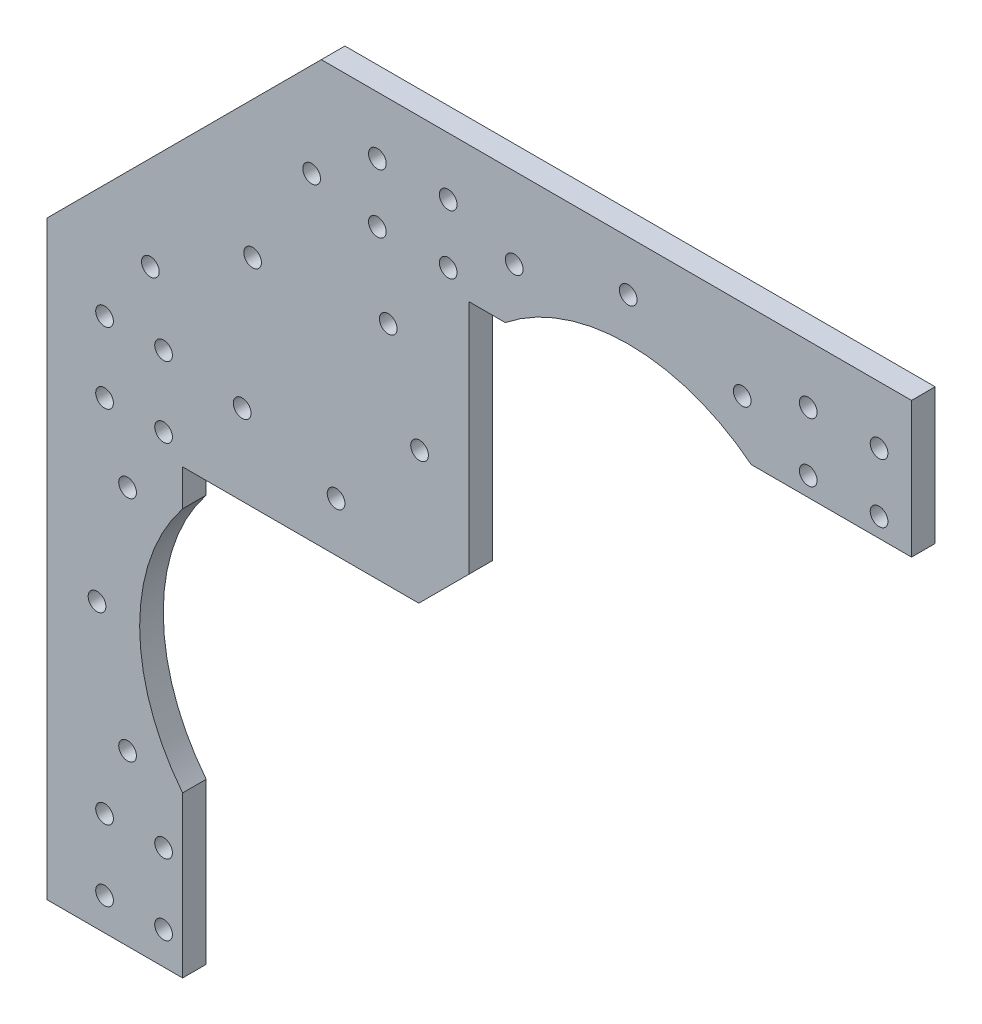
SolidWorks part; units mm, degrees
ref_plane "Front Plane" through (0, 0, 0) normal (0, 0, 1) x (1, 0, 0)
ref_plane "Top Plane" through (0, 0, 0) normal (0, 1, 0) x (1, 0, 0)
ref_plane "Right Plane" through (0, 0, 0) normal (1, 0, 0) x (0, 0, -1)
sketch "Sketch1" plane through (0, 0, 0) normal (0, 0, 1) x (1, 0, 0)
  line L0 (0, 0) -> (0, 75.5) construction
  line L1 (-98.5, -48) -> (-75.5, -48)
  line L2 (-98.5, -48) -> (-98.5, 52)
  line L4 (-75.5, -48) -> (-75.5, 27) construction
  line L5 (-52, 98.5) -> (48, 98.5)
  line L7 (-27, 75.5) -> (48, 75.5) construction
  line L8 (48, 98.5) -> (48, 75.5)
  line L9 (0, 0) -> (-75.5, 0) construction
  line L10 (-27, 75.5) -> (-75.5, 27) construction
  line L11 (-75.5, 75.5) -> (-27, 75.5) construction
  line L12 (-75.5, 27) -> (-75.5, 75.5) construction
  line L13 (-52, 98.5) -> (-98.5, 52)
  line L14 (-98.5, 98.5) -> (-52, 98.5) construction
  line L15 (-98.5, 52) -> (-98.5, 98.5) construction
  line L16 (-20.8425, 75.5) -> (-27, 75.5)
  line L17 (20.8425, 75.5) -> (48, 75.5)
  line L18 (-75.5, 27) -> (-75.5, 20.8425)
  line L19 (-75.5, -48) -> (-75.5, -20.8425)
  line L20 (-75.5, 20.8425) -> (-75.5, -20.8425) construction
  line L21 (-20.8425, 75.5) -> (20.8425, 75.5) construction
  line L22 (-75.5, 27) -> (-35.4853, 27)
  line L23 (-27, 35.4853) -> (-27, 75.5)
  line L24 (-35.4853, 27) -> (-27, 35.4853)
  arc A0 (20.8425, 75.5) -> (-20.8425, 75.5) centre (0, 49.3) ccw
  arc A1 (-75.5, 20.8425) -> (-75.5, -20.8425) centre (-49.3, 0) ccw
  dimension "D6" = 33.4791
  dimension "D1" = 135
  dimension "D2" = 23
  dimension "D3" = 75.5
  dimension "D4" = 48
  dimension "D8" = 27
  dimension "D9" = 12
  dimension "D5" = 100
  dimension "D7" = 26.2
extrude "Boss-Extrude1" add sketch "Sketch1" along normal blind 4
ref_axis "Axis1" through (0, 0, -0.2) along (0, 0, 1)
sketch "Sketch3" plane through (0, 0, 4) normal (0, 0, 1) x (1, 0, 0)
  line L1 (30.5, 88.7259) -> (30.5, 78.7259) construction
  line L2 (30.5, 88.7259) -> (42.5, 88.7259) construction
  line L3 (42.5, 88.7259) -> (42.5, 78.7259) construction
  line L4 (30.5, 78.7259) -> (42.5, 78.7259) construction
  line L16 (-30.5, 78.7259) -> (0, 78.7259) construction
  line L17 (0, 78.7259) -> (0, 0) construction
  line L18 (0, 78.7259) -> (30.5, 78.7259) construction
  line L19 (-78.7259, 0) -> (0, 0) construction
  line L20 (-78.7259, -30.5) -> (-78.7259, 0) construction
  line L21 (-78.7259, 0) -> (-78.7259, 30.5) construction
  line L30 (-42.5, 88.7259) -> (-42.5, 78.7259) construction
  line L31 (-42.5, 88.7259) -> (-30.5, 88.7259) construction
  line L32 (-30.5, 88.7259) -> (-30.5, 78.7259) construction
  line L33 (-42.5, 78.7259) -> (-30.5, 78.7259) construction
  line L34 (-88.7259, 42.5) -> (-88.7259, 30.5) construction
  line L35 (-88.7259, 42.5) -> (-78.7259, 42.5) construction
  line L36 (-78.7259, 42.5) -> (-78.7259, 30.5) construction
  line L37 (-88.7259, 30.5) -> (-78.7259, 30.5) construction
  line L38 (-88.7259, -30.5) -> (-88.7259, -42.5) construction
  line L39 (-88.7259, -30.5) -> (-78.7259, -30.5) construction
  line L40 (-78.7259, -30.5) -> (-78.7259, -42.5) construction
  line L41 (-88.7259, -42.5) -> (-78.7259, -42.5) construction
  circle A0 centre (30.5, 78.7259) radius 1.5
  circle A1 centre (30.5, 88.7259) radius 1.5
  circle A2 centre (42.5, 88.7259) radius 1.5
  circle A3 centre (42.5, 78.7259) radius 1.5
  circle A24 centre (-42.5, 78.7259) radius 1.5
  circle A25 centre (-42.5, 88.7259) radius 1.5
  circle A26 centre (-30.5, 88.7259) radius 1.5
  circle A27 centre (-30.5, 78.7259) radius 1.5
  circle A28 centre (-88.7259, 30.5) radius 1.5
  circle A29 centre (-88.7259, 42.5) radius 1.5
  circle A30 centre (-78.7259, 42.5) radius 1.5
  circle A31 centre (-78.7259, 30.5) radius 1.5
  circle A32 centre (-88.7259, -42.5) radius 1.5
  circle A33 centre (-88.7259, -30.5) radius 1.5
  circle A34 centre (-78.7259, -30.5) radius 1.5
  circle A35 centre (-78.7259, -42.5) radius 1.5
  point P8 (30.5, 78.7259)
  point P12 (33.0196, 82.4917)
  point P15 (30.5, 78.7259)
  point P17 (36.7833, 83.4447)
  point P27 (0, 0)
  point P46 (0, 0)
  point P47 (0, 0)
  dimension "D1" = 3
  dimension "D8" = 30.5
  dimension "D2" = 12
  dimension "D6" = 10
  dimension "D3" = 78.7259
extrude "Cut-Extrude1" cut sketch "Sketch3" against normal blind 10
sketch "Sketch4" plane through (0, 0, 4) normal (0, 0, 1) x (1, 0, 0)
  line L0 (0, 0) -> (0, 90) construction
  line L1 (0, 0) -> (-63.6396, 63.6396) construction
  line L2 (0, 0) -> (-90, 0) construction
  line L3 (-84.8236, 19.3185) -> (-90, 0) construction
  line L4 (-90, 0) -> (-84.8236, -19.3185) construction
  line L5 (-80.9601, 53.6396) -> (-63.6396, 63.6396) construction
  line L6 (-63.6396, 63.6396) -> (-83.2677, 83.2677) construction
  line L7 (-19.3185, 84.8236) -> (0, 90) construction
  line L8 (-65.4074, 40.6586) -> (-40.6586, 65.4074) construction
  line L9 (-35.3553, 49.4975) -> (-49.4975, 35.3553) construction
  line L10 (-75.5, -48) -> (-75.5, -20.8425) construction
  line L11 (-35.4853, 27) -> (-27, 35.4853) construction
  circle A0 centre (-90, 0) radius 1.5
  circle A1 centre (-63.6396, 63.6396) radius 1.5
  circle A2 centre (0, 90) radius 1.5
  circle A3 centre (-80.9601, 53.6396) radius 1.5
  circle A4 centre (-53.6396, 80.9601) radius 1.5
  circle A5 centre (19.3185, 84.8236) radius 1.5
  circle A6 centre (-19.3185, 84.8236) radius 1.5
  circle A7 centre (-84.8236, 19.3185) radius 1.5
  circle A8 centre (-84.8236, -19.3185) radius 1.5
  circle A9 centre (-40.6586, 65.4074) radius 1.5
  circle A10 centre (-65.4074, 40.6586) radius 1.5
  circle A11 centre (-49.4975, 35.3553) radius 1.5
  circle A12 centre (-35.3553, 49.4975) radius 1.5
  dimension "D2" = 3
  dimension "D1" = 45
  dimension "D3" = 14.5
  dimension "D4" = 75
  dimension "D5" = 20
  dimension "D6" = 45.8162
  dimension "D7" = 75
  dimension "D8" = 75
  dimension "D9" = 35
  dimension "D10" = 20
  dimension "D11" = 15
  dimension "D12" = 15
extrude "Cut-Extrude2" cut sketch "Sketch4" against normal through all
equation "\"EyeDiameter\" = 35"
equation "\"BasePlaneDistance\" = \"EyeDiameter\"/2+19.84"
equation "\"EyeClearance\" = 2"
equation "\"L2Thickness\" = 8"
equation "\"L2_ID\" = 20"
equation "\"D3@Sketch1\"= \"BasePlaneDistance\" + 38.16"
equation "\"D3@Sketch3\"=\"BasePlaneDistance\" - 37.34+78.72592343"
